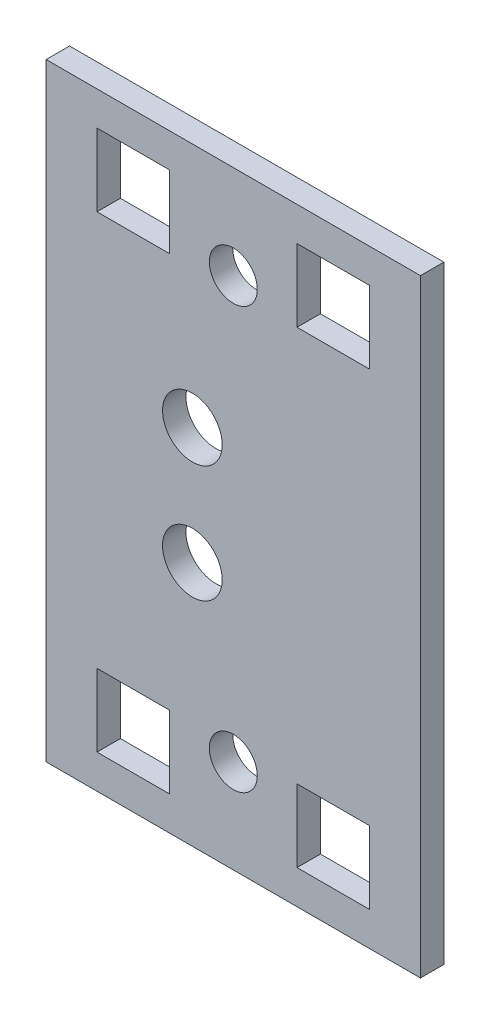
SolidWorks part; units mm, degrees
ref_plane "前视基准面" through (0, 0, 0) normal (0, 0, 1) x (1, 0, 0)
ref_plane "上视基准面" through (0, 0, 0) normal (0, 1, 0) x (1, 0, 0)
ref_plane "右视基准面" through (0, 0, 0) normal (1, 0, 0) x (0, 0, -1)
sketch "草图1" plane through (0, 0, 0) normal (0, 0, 1) x (1, 0, 0)
  line L0 (-10.3431, 0) -> (44.8563, 0) construction
  line L1 (38.1298, -5) -> (38.1298, -19.6678) construction
  line L2 (43.5798, -16.9) -> (43.5798, -23.1)
  line L3 (26.4798, -16.9) -> (32.6798, -16.9)
  line L4 (26.4798, -16.9) -> (26.4798, -23.1)
  line L5 (26.4798, -23.1) -> (32.6798, -23.1)
  line L6 (32.6798, -16.9) -> (32.6798, -23.1)
  line L7 (26.4798, -16.9) -> (32.6798, -23.1) construction
  line L8 (26.4798, -23.1) -> (32.6798, -16.9) construction
  line L9 (49.7798, -23.1) -> (43.5798, -23.1)
  line L10 (49.7798, -16.9) -> (49.7798, -23.1)
  line L11 (49.7798, -16.9) -> (43.5798, -16.9)
  line L12 (32.6798, 16.9) -> (32.6798, 23.1)
  line L13 (26.4798, 23.1) -> (32.6798, 23.1)
  line L14 (26.4798, 16.9) -> (32.6798, 16.9)
  line L15 (26.4798, 16.9) -> (26.4798, 23.1)
  line L16 (43.5798, 16.9) -> (43.5798, 23.1)
  line L17 (49.7798, 23.1) -> (43.5798, 23.1)
  line L18 (49.7798, 16.9) -> (49.7798, 23.1)
  line L19 (49.7798, 16.9) -> (43.5798, 16.9)
  line L20 (43.5798, -16.9) -> (32.6798, 16.9) construction
  line L21 (29.5798, -20) -> (29.5798, -18) construction
  line L22 (54.1298, -26) -> (22.1298, -26)
  line L23 (54.1298, -26) -> (54.1298, 26)
  line L24 (54.1298, 26) -> (22.1298, 26)
  line L25 (22.1298, -26) -> (22.1298, 26)
  line L26 (54.1298, -26) -> (22.1298, 26) construction
  line L27 (54.1298, 26) -> (22.1298, -26) construction
  line L28 (29.5798, -18) -> (46.6798, -18) construction
  circle A0 centre (34.6298, 5) radius 2.55
  circle A1 centre (38.1298, -18) radius 2.05
  circle A2 centre (34.6298, -5) radius 2.55
  circle A3 centre (38.1298, 18) radius 2.05
  point P8 (29.5798, -20)
  point P10 (38.1298, 0)
  point P19 (46.6798, -20)
  point P28 (46.6798, 20)
  dimension "D2" = 32
  dimension "D7" = 52
  dimension "D9" = 4.1
  dimension "D1" = 5
  dimension "D3" = 3.5
  dimension "D4" = 6.2
  dimension "D5" = 6.2
  dimension "D6" = 17.1
  dimension "D8" = 40
extrude "凸台-拉伸1" add sketch "草图1" along normal blind 2
